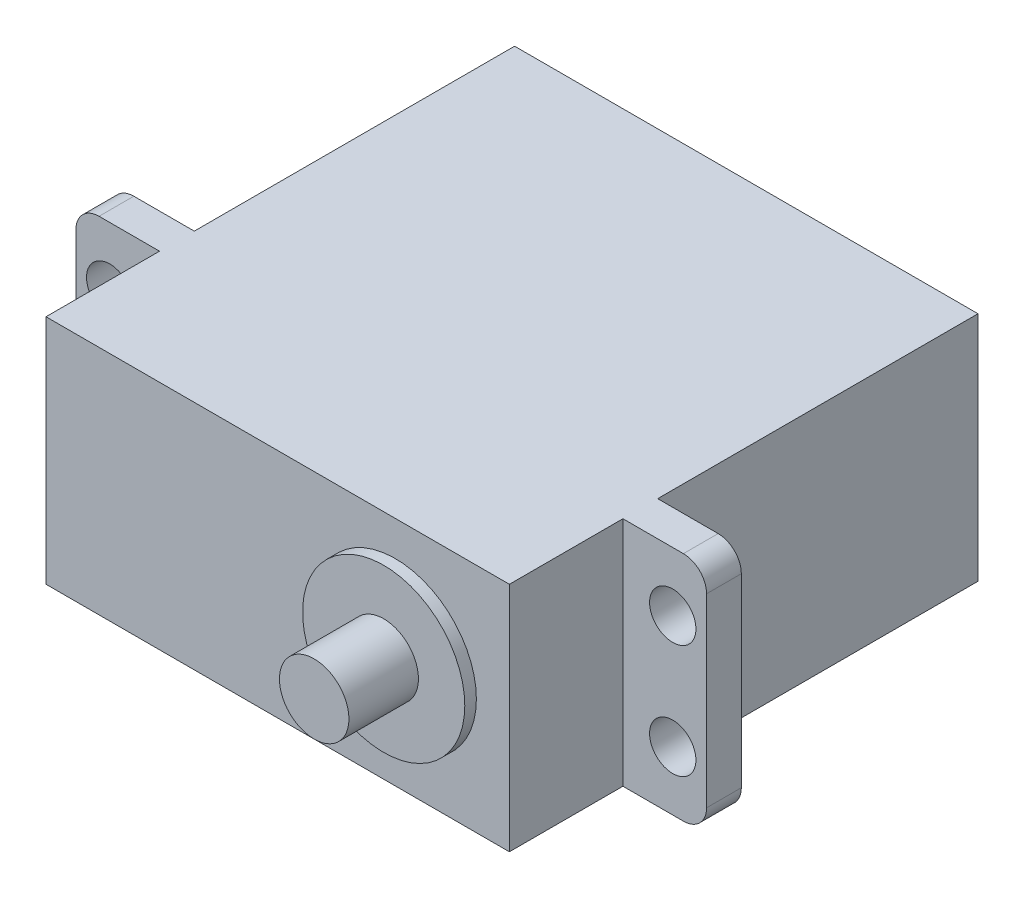
SolidWorks part; units mm, degrees
ref_plane "Front Plane" through (0, 0, 0) normal (0, 0, 1) x (1, 0, 0)
ref_plane "Top Plane" through (0, 0, 0) normal (0, 1, 0) x (1, 0, 0)
ref_plane "Right Plane" through (0, 0, 0) normal (1, 0, 0) x (0, 0, -1)
sketch "Sketch2" plane through (0, 0, 0) normal (0, 0, 1) x (1, 0, 0)
  line L1 (-13.5922, 208.3879) -> (-53.5922, 208.3879)
  line L2 (-13.5922, 208.3879) -> (-13.5922, 228.3879)
  line L3 (-13.5922, 228.3879) -> (-53.5922, 228.3879)
  line L4 (-53.5922, 208.3879) -> (-53.5922, 228.3879)
  dimension "D1" = 40
  dimension "D2" = 20
extrude "Boss-Extrude1" add sketch "Sketch2" along normal blind 27.65
sketch "Sketch3" plane through (0, 0, 27.65) normal (0, 0, 1) x (1, 0, 0)
  line L0 (-53.5922, 208.3879) -> (-13.5922, 208.3879) construction
  line L1 (-6.3722, 208.3879) -> (-60.8122, 208.3879)
  line L2 (-6.3722, 208.3879) -> (-6.3722, 228.3879)
  line L3 (-6.3722, 228.3879) -> (-60.8122, 228.3879)
  line L4 (-60.8122, 208.3879) -> (-60.8122, 228.3879)
  line L5 (-13.5922, 228.3879) -> (-53.5922, 228.3879) construction
  line L6 (-13.5922, 218.3879) -> (-53.5922, 218.3879) construction
  line L7 (-13.5922, 208.3879) -> (-13.5922, 228.3879) construction
  line L8 (-53.5922, 228.3879) -> (-53.5922, 208.3879) construction
  line L9 (-33.5922, 218.3879) -> (-33.5922, 214.2288) construction
  circle A0 centre (-9.2922, 213.4879) radius 2
  circle A1 centre (-9.2922, 223.2879) radius 2
  circle A2 centre (-57.8922, 223.2879) radius 2
  circle A3 centre (-57.8922, 213.4879) radius 2
  dimension "D1" = 0
  dimension "D2" = 0
  dimension "D3" = 54.44
  dimension "D4" = 27.22
extrude "Boss-Extrude2" add sketch "Sketch3" along normal blind 3
sketch "Sketch4" plane through (0, 0, 30.65) normal (0, 0, 1) x (1, 0, 0)
  line L4 (-13.5922, 208.3879) -> (-13.5922, 228.3879)
  line L5 (-53.5922, 208.3879) -> (-13.5922, 208.3879)
  line L6 (-53.5922, 228.3879) -> (-53.5922, 208.3879)
  line L7 (-13.5922, 228.3879) -> (-53.5922, 228.3879)
  line L8 (-13.5922, 208.3879) -> (-13.5922, 228.3879)
  line L9 (-53.5922, 208.3879) -> (-13.5922, 208.3879)
  line L10 (-53.5922, 228.3879) -> (-53.5922, 208.3879)
  line L11 (-13.5922, 228.3879) -> (-53.5922, 228.3879)
  dimension "D1" = 0
extrude "Boss-Extrude3" add sketch "Sketch4" along normal blind 9.8
sketch "Sketch5" plane through (0, 0, 40.45) normal (0, 0, 1) x (1, 0, 0)
  circle A0 centre (-23.4422, 218.3879) radius 7
  circle A1 centre (-57.8922, 223.2879) radius 2 construction
  dimension "D1" = 34.45
extrude "Boss-Extrude4" add sketch "Sketch5" along normal blind 1
sketch "Sketch6" plane through (0, 0, 41.45) normal (0, 0, 1) x (1, 0, 0)
  circle A0 centre (-23.4422, 218.3879) radius 3
extrude "Boss-Extrude5" add sketch "Sketch6" along normal blind 6
fillet "Fillet1" radius 2 4 edges at (-60.8122, 228.3879, 29.15) (-60.8122, 208.3879, 29.15) (-6.3722, 228.3879, 29.15) (-6.3722, 208.3879, 29.15)
